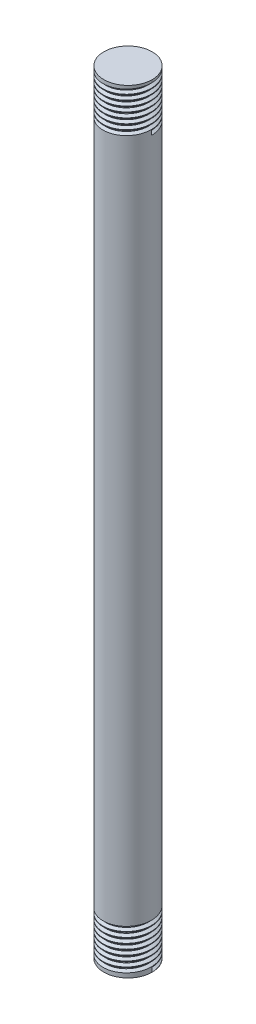
SolidWorks part; units mm, degrees
ref_plane "Front Plane" through (0, 0, 0) normal (0, 0, 1) x (1, 0, 0)
ref_plane "Top Plane" through (0, 0, 0) normal (0, 1, 0) x (1, 0, 0)
ref_plane "Right Plane" through (0, 0, 0) normal (1, 0, 0) x (0, 0, -1)
sketch "Szkic1" plane through (0, 0, 0) normal (0, 1, 0) x (1, 0, 0)
  circle A0 centre (0, 0) radius 5
extrude "Dodanie-wyciągnięcie1" add sketch "Szkic1" along normal blind 160
thread "Gwint1" pitch 1.0583 method cut profile "Profil gwintu1" start angle 0, offset 0, length 9, pitch 1.0583, diameter 10
ref_plane "Płaszczyzna1" through (5, 0, 0) normal (0, 0, 1) x (1, 0, 0)
sketch "Profil gwintu1" plane through (5, 0, 0) normal (0, 0, 1) x (1, 0, 0)
  line L0 (0, 0) -> (0, 1.0583) construction
  line L11 (0, 0) -> (0, 0.926)
  line L12 (0, 0.926) -> (-0.5728, 0.5953)
  line L13 (-0.5728, 0.5953) -> (-0.5728, 0.3307)
  line L15 (-0.5728, 0.3307) -> (0, 0)
  line L17 (-0.5728, 0.463) -> (0, 0.463) construction
  point P2 (0, 0)
  dimension "Pitch" = 1.0583
  dimension "Profile_Angle" = 60
  dimension "Profile_Land" = 0.2646
  dimension "Profile_Height" = 0.5728
thread "Gwint2" pitch 1.0583 method cut profile "Profil gwintu2" start angle 0, offset 0, length 9, pitch 1.0583, diameter 10
ref_plane "Płaszczyzna2" through (-5, 160, 0) normal (0, 0, 1) x (-1, 0, 0)
sketch "Profil gwintu2" plane through (-5, 160, 0) normal (0, 0, 1) x (-1, 0, 0)
  line L0 (0, 0) -> (0, 1.0583) construction
  line L11 (0, 0) -> (0, 0.926)
  line L12 (0, 0.926) -> (-0.5728, 0.5953)
  line L13 (-0.5728, 0.5953) -> (-0.5728, 0.3307)
  line L15 (-0.5728, 0.3307) -> (0, 0)
  line L17 (-0.5728, 0.463) -> (0, 0.463) construction
  point P2 (0, 0)
  dimension "Pitch" = 1.0583
  dimension "Profile_Angle" = 60
  dimension "Profile_Land" = 0.2646
  dimension "Profile_Height" = 0.5728
